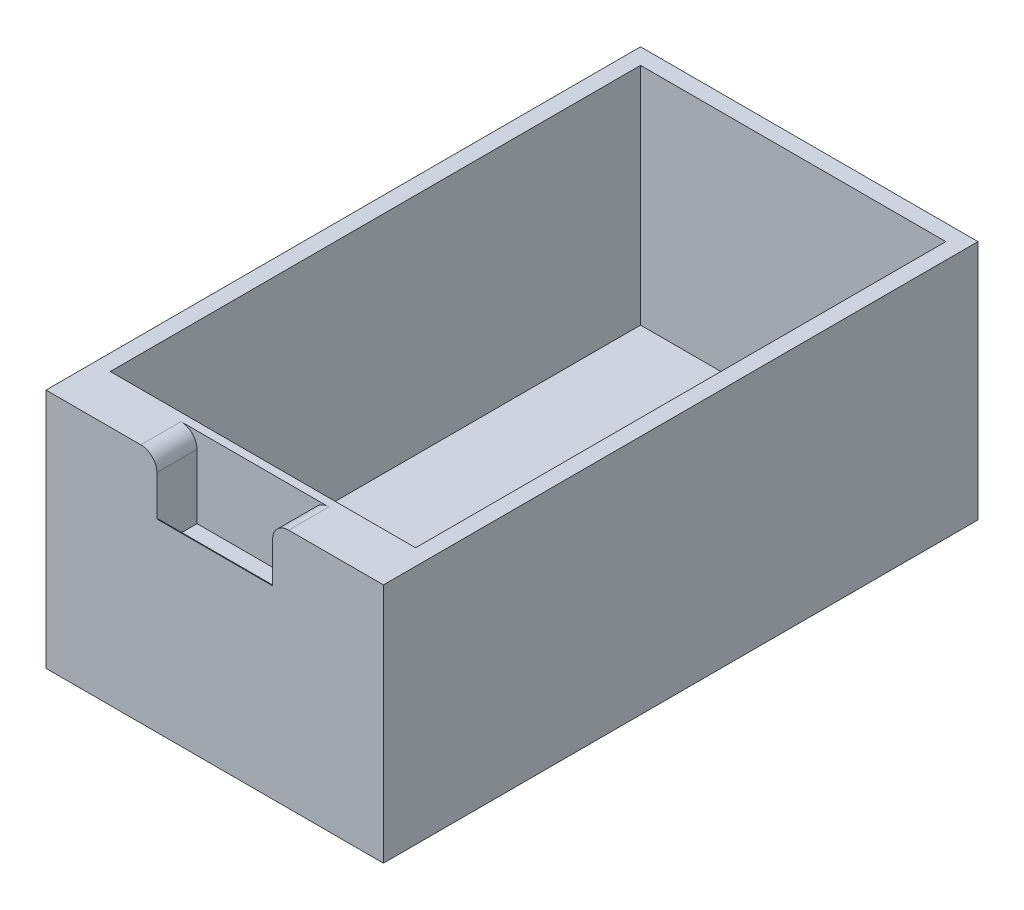
SolidWorks part; units mm, degrees
ref_plane "Plan de face" through (0, 0, 0) normal (0, 0, 1) x (1, 0, 0)
ref_plane "Plan de dessus" through (0, 0, 0) normal (0, 1, 0) x (1, 0, 0)
ref_plane "Plan de droite" through (0, 0, 0) normal (1, 0, 0) x (0, 0, -1)
sketch "Esquisse1" plane through (0, 0, 0) normal (0, 0, 1) x (1, 0, 0)
  line L1 (-159.4773, 63.8235) -> (50.5227, 63.8235)
  line L2 (-159.4773, 63.8235) -> (-159.4773, -86.1765)
  line L3 (-159.4773, -86.1765) -> (50.5227, -86.1765)
  line L4 (50.5227, 63.8235) -> (50.5227, -86.1765)
  dimension "D1" = 150
  dimension "D2" = 210
extrude "Boss.-Extru.1" add sketch "Esquisse1" against normal blind 370
sketch "Esquisse2" plane through (0, 63.8235, 0) normal (0, 1, 0) x (1, 0, 0)
  line L0 (-159.4773, 370) -> (-159.4773, 0) construction
  line L1 (-149.4773, 360) -> (40.5227, 360)
  line L2 (-149.4773, 360) -> (-149.4773, 30)
  line L3 (-149.4773, 30) -> (40.5227, 30)
  line L4 (40.5227, 360) -> (40.5227, 30)
  line L5 (50.5227, 370) -> (50.5227, 0) construction
  line L6 (50.5227, 370) -> (-159.4773, 370) construction
  line L7 (50.5227, 0) -> (-159.4773, 0) construction
  dimension "D1" = 10
  dimension "D2" = 10
  dimension "D3" = 10
  dimension "D4" = 30
extrude "Enlèv. mat.-Extru.1" cut sketch "Esquisse2" against normal blind 140
ref_plane "Plan1" through (-159.4773, -86.1765, 0) normal (1, 0, 0) x (0, 0, -1)
sketch "Esquisse6" plane through (0, 63.8235, 0) normal (0, 1, 0) x (1, 0, 0)
  line L0 (50.5227, 0) -> (-159.4773, 0) construction
  line L1 (-90.4773, 0) -> (-18.4773, 0)
  line L2 (-90.4773, 0) -> (-90.4773, 25)
  line L3 (-90.4773, 25) -> (-18.4773, 25)
  line L4 (-18.4773, 0) -> (-18.4773, 25)
  line L5 (-159.4773, 370) -> (-159.4773, 0) construction
  dimension "D1" = 72
  dimension "D2" = 25
  dimension "D3" = 69
extrude "Enlèv. mat.-Extru.4" cut sketch "Esquisse6" against normal blind 35
sketch "Esquisse7" plane through (0, 28.8235, 0) normal (0, 1, 0) x (1, 0, 0)
  line L0 (-18.4773, 0) -> (-18.4773, 25) construction
  line L1 (-90.4773, 25) -> (-18.4773, 25)
  line L2 (-90.4773, 25) -> (-90.4773, 5)
  line L3 (-90.4773, 5) -> (-18.4773, 5)
  line L4 (-18.4773, 25) -> (-18.4773, 5)
  line L5 (-90.4773, 0) -> (-18.4773, 0) construction
  dimension "D1" = 5
extrude "Enlèv. mat.-Extru.5" cut sketch "Esquisse7" against normal blind 15
fillet "Congé3" radius 10 1 edges at (-90.4773, 63.8235, -12.5)
fillet "Congé4" radius 10 1 edges at (-18.4773, 63.8235, -12.5)
fillet "Congé5" radius 10 1 edges at (-54.4773, 28.8235, -5)
